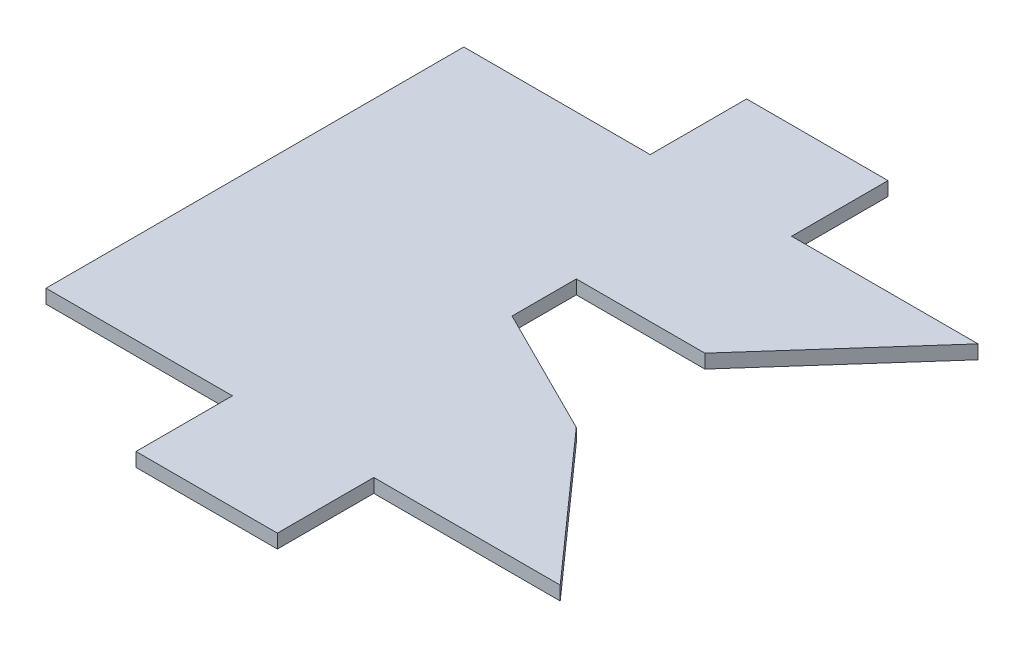
SolidWorks part; units mm, degrees
ref_plane "Front Plane" through (0, 0, 0) normal (0, 0, 1) x (1, 0, 0)
ref_plane "Top Plane" through (0, 0, 0) normal (0, 1, 0) x (1, 0, 0)
ref_plane "Right Plane" through (0, 0, 0) normal (1, 0, 0) x (0, 0, -1)
sketch "Sketch2" plane through (0, 0, 0) normal (0, 1, 0) x (1, 0, 0)
  line L2 (0, 0) -> (0, 65)
  line L3 (0, 65) -> (58, 65)
  line L4 (160, 0) -> (160, 65)
  line L8 (0, 0) -> (160, 0)
  line L9 (102, 65) -> (160, 65)
  line L11 (102, 65) -> (102, 95)
  line L12 (58, 65) -> (58, 95)
  line L13 (58, 95) -> (102, 95)
  dimension "D1" = 65
  dimension "D2" = 160
  dimension "D3" = 44
  dimension "D4" = 30
extrude "Boss-Extrude1" add sketch "Sketch2" along normal blind 4.3
mirror "Mirror1" about plane through (0, 4.3, 0) normal (0, 0, -1) of bodies 101
sketch "Sketch3" plane through (0, 4.3, 0) normal (0, 1, 0) x (1, 0, 0)
  line L0 (160, 65) -> (160, -65)
  line L1 (120.0126, 20) -> (160, 65)
  line L3 (80.0126, 0) -> (80.0126, 20)
  line L4 (80.0126, 20) -> (120.0126, 20)
  line L12 (160, 65) -> (102, 65)
  line L13 (102, 65) -> (102, 95)
  line L15 (102, 95) -> (58, 95)
  line L16 (58, 65) -> (0, 65)
  line L17 (0, 65) -> (0, -65)
  line L18 (0, -65) -> (58, -65)
  line L20 (58, 95) -> (58, 65)
  line L22 (102, -65) -> (160, -65)
  line L23 (160, -65) -> (160, 65)
  line L36 (58, -65) -> (58, -95)
  line L38 (58, -95) -> (102, -95)
  line L39 (58, -95) -> (102, -95)
  line L40 (102, -95) -> (102, -65)
  line L48 (80.0126, 0) -> (120, -20)
  line L49 (120, -20) -> (160, -65)
  line M24 (160, -65) -> (160, 65)
  dimension "D2" = 130
  dimension "D3" = 20
  dimension "D4" = 40
  dimension "D1" = 0
extrude "Cut-Extrude1" cut sketch "Sketch3" against normal blind 4.5 contours L48 L49 L1 L4 L3 M24 region at (132.7576, 4.3, -1.1571)
